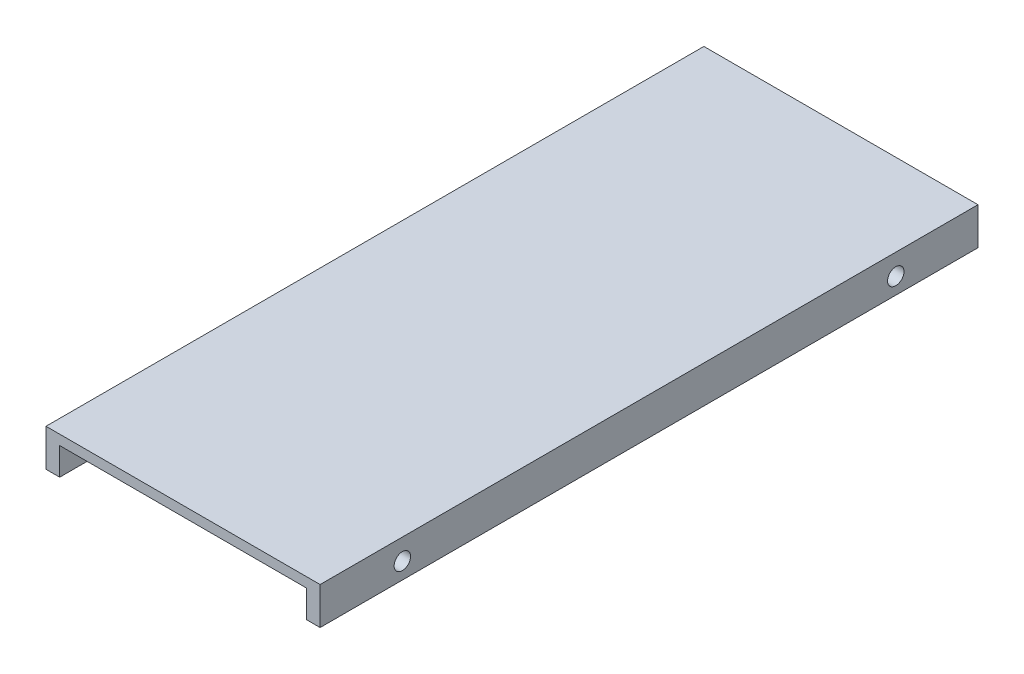
SolidWorks part; units mm, degrees
ref_plane "Front Plane" through (0, 0, 0) normal (0, 0, 1) x (1, 0, 0)
ref_plane "Top Plane" through (0, 0, 0) normal (0, 1, 0) x (1, 0, 0)
ref_plane "Right Plane" through (0, 0, 0) normal (1, 0, 0) x (0, 0, -1)
sketch "Sketch1" plane through (0, 0, 0) normal (0, 0, 1) x (1, 0, 0)
  line L1 (0, 0) -> (500, 0)
  line L2 (0, 0) -> (0, 18)
  line L3 (0, 18) -> (500, 18)
  line L4 (500, 0) -> (500, 18)
  line L5 (0, 0) -> (25, 0)
  line L6 (0, 0) -> (0, -50)
  line L7 (0, -50) -> (25, -50)
  line L8 (25, 0) -> (25, -50)
  line L9 (500, 0) -> (475, 0)
  line L10 (500, 0) -> (500, -50)
  line L11 (500, -50) -> (475, -50)
  line L12 (475, 0) -> (475, -50)
  dimension "D1" = 68
  dimension "D2" = 25
  dimension "D3" = 18
  dimension "D4" = 25
  dimension "D5" = 500
extrude "Boss-Extrude1" add sketch "Sketch1" along normal blind 1200 contours L8 L1 L6 L7 | L1 L4 L3 L2 | L1 L12 L11 L10 region at (250, 9, 0) region at (12.5, -25, 0) region at (487.5, -25, 0)
sketch "Sketch2" plane through (500, 0, 0) normal (1, 0, 0) x (0, 0, -1)
  line L0 (0, -50) -> (0, 18) construction
  line L1 (-1200, -50) -> (0, -50) construction
  line L2 (-1200, -50) -> (-1200, 18) construction
  circle A0 centre (-1050, -20) radius 15
  circle A1 centre (-150, -20) radius 15
  point P4 (0, 0)
  dimension "D1" = 30
  dimension "D2" = 150
  dimension "D3" = 30
  dimension "D4" = 150
extrude "Cut-Extrude1" cut sketch "Sketch2" against normal through all both and the other way through all
